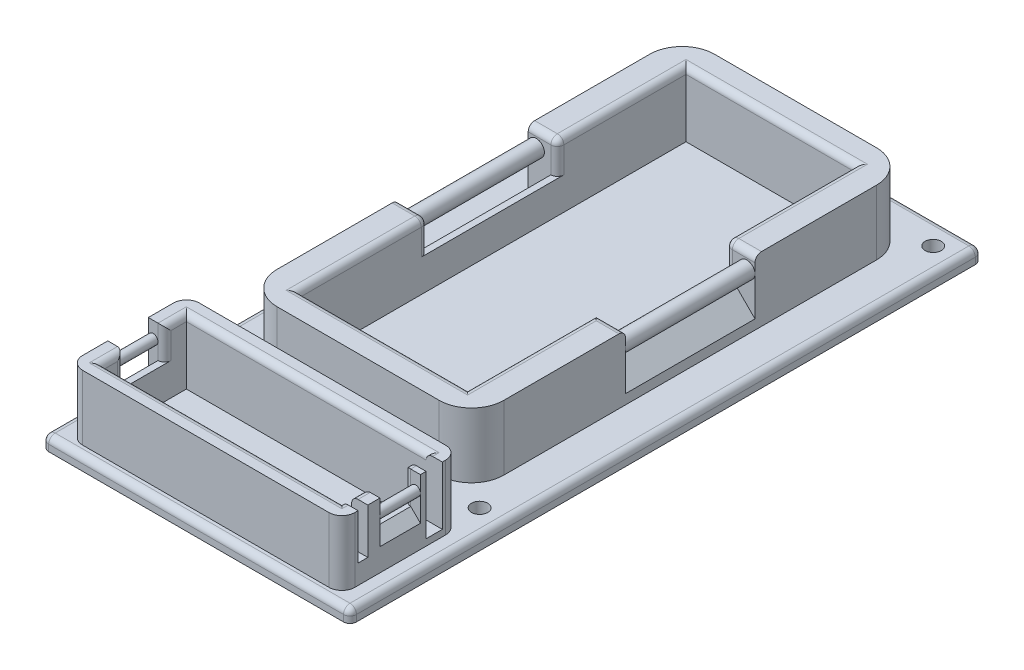
SolidWorks part; units mm, degrees
material "Delrin 2700 NC010, Low Viscosity Acetal Copolymer (SS)"
ref_plane "Front Plane" through (0, 0, 0) normal (0, 0, 1) x (1, 0, 0)
ref_plane "Top Plane" through (0, 0, 0) normal (0, 1, 0) x (1, 0, 0)
ref_plane "Right Plane" through (0, 0, 0) normal (1, 0, 0) x (0, 0, -1)
sketch "Sketch1" plane through (0, 0, 0) normal (0, 1, 0) x (1, 0, 0)
  line L0 (-60.325, -98.425) -> (-60.325, -149.225)
  line L2 (-60.325, -98.425) -> (-60.325, 98.425)
  line L3 (-60.325, 98.425) -> (60.325, 98.425)
  line L4 (60.325, -98.425) -> (60.325, 98.425)
  line L5 (-60.325, -98.425) -> (60.325, 98.425) construction
  line L6 (-60.325, 98.425) -> (60.325, -98.425) construction
  line L7 (-50.8, -88.9) -> (50.8, -88.9) construction
  line L8 (-50.8, -88.9) -> (-50.8, 88.9) construction
  line L9 (-50.8, 88.9) -> (50.8, 88.9) construction
  line L10 (50.8, -88.9) -> (50.8, 88.9) construction
  line L11 (-50.8, -88.9) -> (50.8, 88.9) construction
  line L12 (-50.8, 88.9) -> (50.8, -88.9) construction
  line L13 (-60.325, -149.225) -> (60.325, -149.225)
  line L14 (60.325, -149.225) -> (60.325, -98.425)
  circle A0 centre (-50.8, 88.9) radius 3.175
  circle A1 centre (50.8, 88.9) radius 3.175
  circle A2 centre (50.8, -88.9) radius 3.175
  circle A3 centre (-50.8, -88.9) radius 3.175
  point P0 (0, 0)
  point P6 (0, 0)
  dimension "D5" = 6.35
  dimension "D1" = 120.65
  dimension "D2" = 196.85
  dimension "D3" = 101.6
  dimension "D4" = 177.8
  dimension "D6" = 50.8
extrude "Boss-Extrude1" add sketch "Sketch1" along normal blind 5.08
sketch "Sketch2" plane through (0, 5.08, 0) normal (0, 1, 0) x (1, 0, 0)
  line L1 (-33.02, -75.819) -> (33.02, -75.819)
  line L2 (-33.02, -75.819) -> (-33.02, 75.819)
  line L3 (-33.02, 75.819) -> (33.02, 75.819)
  line L4 (33.02, -75.819) -> (33.02, 75.819)
  line L5 (-33.02, -75.819) -> (33.02, 75.819) construction
  line L6 (-33.02, 75.819) -> (33.02, -75.819) construction
  line L7 (31.75, -85.725) -> (-31.75, -85.725)
  line L8 (44.45, -73.025) -> (44.45, 73.025)
  line L9 (31.75, 85.725) -> (-31.75, 85.725)
  line L10 (-44.45, -73.025) -> (-44.45, 73.025)
  line L11 (44.45, -85.725) -> (-44.45, 85.725) construction
  line L12 (44.45, 85.725) -> (-44.45, -85.725) construction
  arc A0 (-44.45, -73.025) -> (-31.75, -85.725) centre (-31.75, -73.025) ccw
  arc A1 (44.45, -73.025) -> (31.75, -85.725) centre (31.75, -73.025) cw
  arc A2 (31.75, 85.725) -> (44.45, 73.025) centre (31.75, 73.025) cw
  arc A3 (-31.75, 85.725) -> (-44.45, 73.025) centre (-31.75, 73.025) ccw
  point P0 (0, 0)
  point P6 (0, 0)
  dimension "D3" = 12.7
  dimension "D1" = 66.04
  dimension "D2" = 151.638
  dimension "D4" = 171.45
  dimension "D5" = 88.9
extrude "Boss-Extrude2" add sketch "Sketch2" along normal blind 25.4
sketch "Sketch3" plane through (0, 0, 0) normal (1, 0, 0) x (0, 0, -1)
  line L0 (-73.025, 30.48) -> (73.025, 30.48) construction
  line L1 (-25.4, 30.48) -> (25.4, 30.48)
  line L2 (-25.4, 30.48) -> (-25.4, 17.78)
  line L3 (-25.4, 17.78) -> (25.4, 17.78)
  line L4 (25.4, 30.48) -> (25.4, 17.78)
  line L5 (0, 17.78) -> (0, 0) construction
  dimension "D1" = 50.8
  dimension "D2" = 12.7
extrude "Cut-Extrude1" cut sketch "Sketch3" against normal mid plane 152.4
sketch "Sketch4" plane through (0, 0, 25.4) normal (0, 0, -1) x (-1, 0, 0)
  line L0 (-44.45, 17.78) -> (-44.45, 30.48) construction
  line L1 (-33.02, 17.78) -> (-44.45, 17.78) construction
  circle A0 centre (-41.275, 24.13) radius 3.175
  dimension "D1" = 6.35
  dimension "D2" = 0
  dimension "D3" = 6.35
extrude "Boss-Extrude3" add sketch "Sketch4" along normal up to next
mirror "Mirror1" about plane through (0, 0, 0) normal (1, 0, 0) of "Boss-Extrude3"
sketch "Sketch6" plane through (0, 5.08, 0) normal (0, 1, 0) x (1, 0, 0)
  line L0 (-46.99, -139.065) -> (46.99, -139.065)
  line L1 (-53.34, -99.695) -> (53.34, -99.695)
  line L2 (-53.34, -99.695) -> (-53.34, -145.415)
  line L3 (-53.34, -145.415) -> (53.34, -145.415)
  line L4 (53.34, -99.695) -> (53.34, -145.415)
  line L5 (-53.34, -99.695) -> (53.34, -145.415) construction
  line L6 (-53.34, -145.415) -> (53.34, -99.695) construction
  line L7 (46.99, -106.045) -> (46.99, -139.065)
  line L8 (-46.99, -106.045) -> (46.99, -106.045)
  line L9 (-46.99, -106.045) -> (-46.99, -139.065)
  line L10 (-60.325, -149.225) -> (60.325, -149.225) construction
  point P0 (0, -122.555)
  point P9 (46.99, -122.555)
  point P12 (0, -149.225)
  dimension "D2" = 93.98
  dimension "D3" = 33.02
  dimension "D4" = 0
  dimension "D5" = 3.81
  dimension "D1" = 6.35
extrude "Boss-Extrude4" add sketch "Sketch6" along normal blind 25.4
sketch "Sketch8" plane through (0, 30.48, 0) normal (0, 1, 0) x (1, 0, 0)
  line L1 (46.99, -130.4925) -> (53.34, -130.4925)
  line L2 (46.99, -130.4925) -> (46.99, -114.6175)
  line L3 (46.99, -114.6175) -> (53.34, -114.6175)
  line L4 (53.34, -130.4925) -> (53.34, -114.6175)
  line L5 (46.99, -139.065) -> (46.99, -106.045) construction
  line L6 (53.34, -145.415) -> (53.34, -99.695) construction
  point P4 (46.99, -122.555)
  point P9 (53.34, -122.555)
  dimension "D1" = 15.875
extrude "Cut-Extrude2" cut sketch "Sketch8" against normal blind 12.7
sketch "Sketch10" plane through (0, 0, 130.4925) normal (0, 0, -1) x (-1, 0, 0)
  line L0 (-53.34, 17.78) -> (-53.34, 30.48) construction
  circle A0 centre (-51.435, 24.13) radius 1.905
  point P4 (-53.34, 24.13)
  dimension "D1" = 3.81
  dimension "D2" = 0
  dimension "D3" = 0
extrude "Boss-Extrude5" add sketch "Sketch10" along normal up to surface (15.875 mm away) contours A0 up to face at (50.165, 24.13, 114.6175)
mirror "Mirror2" about plane through (0, 0, 0) normal (1, 0, 0) of "Boss-Extrude5", "Cut-Extrude2"
fillet "Fillet6" radius 2.54 10 edges at (0, 30.48, 106.045) (46.99, 30.48, 110.3312) (-46.99, 24.13, 114.6175) (-46.99, 24.13, 130.4925) (-46.99, 30.48, 110.3312) (-46.99, 30.48, 134.7788) (0, 30.48, 139.065) (46.99, 30.48, 134.7788) (46.99, 24.13, 114.6175) (46.99, 24.13, 130.4925)
fillet "Fillet7" radius 2.54 4 edges at (60.325, 5.08, 25.4) (0, 5.08, -98.425) (0, 5.08, 149.225) (-60.325, 5.08, 25.4)
fillet "Fillet8" radius 2.54 8 edges at (60.325, 1.27, 149.225) (-60.325, 1.27, 149.225) (60.325, 1.27, -98.425) (-60.325, 1.27, -98.425) (59.5811, 4.3361, 148.4811) (-59.5811, 4.3361, 148.4811) (59.5811, 4.3361, -97.6811) (-59.5811, 4.3361, -97.6811)
fillet "Fillet9" radius 5.08 4 edges at (53.34, 17.78, 99.695) (53.34, 17.78, 145.415) (-53.34, 17.78, 99.695) (-53.34, 17.78, 145.415)
chamfer "Chamfer2" distance 8.89 angle 45 1 edges at (-44.45, 17.78, 0)
fillet "Fillet10" radius 2.54 2 edges at (-33.02, 24.13, 25.4) (-33.02, 24.13, -25.4)
fillet "Fillet5" radius 2.54 13 edges at (0, 30.48, -75.819) (33.02, 30.48, -50.6095) (33.02, 30.48, 50.6095) (0, 30.48, 75.819) (-33.02, 30.48, 51.8795) (-33.02, 30.48, -51.8795) (33.02, 24.13, -25.4) (-40.005, 30.48, 25.4) (-33.7639, 30.48, 26.1439) (-40.005, 30.48, -25.4) (-33.7639, 30.48, -26.1439) (38.735, 30.48, -25.4) (38.735, 30.48, 25.4)
chamfer "Chamfer3" distance 8.89 angle 45 1 edges at (44.45, 17.78, 0)
chamfer "Chamfer5" distance 3.81 angle 45 1 edges at (53.34, 17.78, 122.555)
chamfer "Chamfer6" distance 3.81 angle 45 1 edges at (-53.34, 17.78, 122.555)
sketch "Sketch12" plane through (0, 5.08, 0) normal (0, 1, 0) x (1, 0, 0)
  line L0 (53.34, -140.335) -> (53.34, -104.775) construction
  line L1 (46.99, -106.045) -> (53.34, -106.045)
  line L2 (46.99, -106.045) -> (46.99, -112.395)
  line L3 (46.99, -112.395) -> (53.34, -112.395)
  line L4 (53.34, -106.045) -> (53.34, -112.395)
  line L5 (46.99, -106.045) -> (53.34, -112.395) construction
  line L6 (46.99, -112.395) -> (53.34, -106.045) construction
  point P4 (50.165, -109.22)
  dimension "D1" = 0
  dimension "D2" = 6.35
extrude "Cut-Extrude3" cut sketch "Sketch12" along normal through all from offset 2.54
sketch "Sketch13" plane through (0, 5.08, 0) normal (0, 1, 0) x (1, 0, 0)
  line L1 (46.99, -139.065) -> (53.34, -139.065)
  line L2 (46.99, -139.065) -> (46.99, -135.255)
  line L3 (46.99, -135.255) -> (53.34, -135.255)
  line L4 (53.34, -139.065) -> (53.34, -135.255)
  line L5 (46.99, -139.065) -> (53.34, -135.255) construction
  line L6 (46.99, -135.255) -> (53.34, -139.065) construction
  line L7 (53.34, -140.335) -> (53.34, -130.4925) construction
  point P4 (50.165, -137.16)
  dimension "D1" = 3.81
  dimension "D2" = 0
extrude "Cut-Extrude4" cut sketch "Sketch13" along normal through all from offset 7.62
